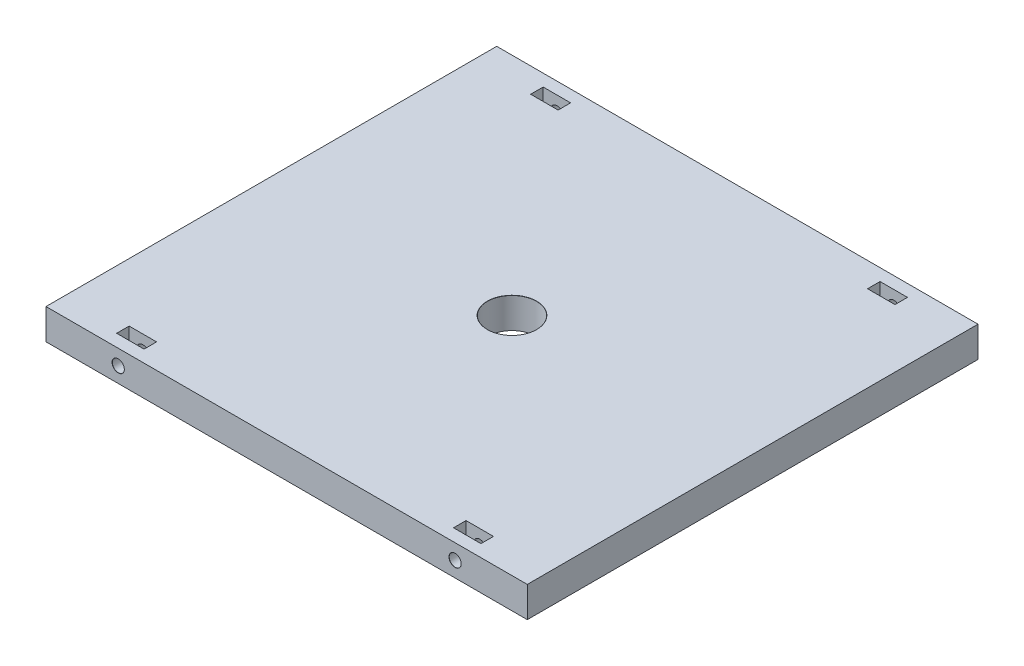
SolidWorks part; units mm, degrees
material "6061 Alloy"
ref_plane "Front Plane" through (0, 0, 0) normal (0, 0, 1) x (1, 0, 0)
ref_plane "Top Plane" through (0, 0, 0) normal (0, 1, 0) x (1, 0, 0)
ref_plane "Right Plane" through (0, 0, 0) normal (1, 0, 0) x (0, 0, -1)
sketch "Sketch1" plane through (0, 0, 0) normal (0, 1, 0) x (1, 0, 0)
  line L1 (-50, -46.825) -> (50, -46.825)
  line L2 (-50, -46.825) -> (-50, 46.825)
  line L3 (-50, 46.825) -> (50, 46.825)
  line L4 (50, -46.825) -> (50, 46.825)
  line L5 (-50, -46.825) -> (50, 46.825) construction
  line L6 (-50, 46.825) -> (50, -46.825) construction
  point P0 (0, 0)
extrude "Boss-Extrude1" add sketch "Sketch1" along normal blind 6.35
sketch "Sketch2" plane through (0, 0, 46.825) normal (0, 0, 1) x (1, 0, 0)
  line L0 (-50, 3.175) -> (-35, 3.175)
  line L1 (-50, 6.35) -> (-50, 0) construction
  line L2 (50, 3.175) -> (35, 3.175)
  line L3 (50, 6.35) -> (50, 0) construction
hole_wizard "Tap Drill for M3x0.5 Tap1" positions "Sketch3" profile "Sketch4" hole size "M3x0.5" standard "ANSI Metric"
sketch "Sketch3" plane through (0, 0, 46.825) normal (0, 0, 1) x (1, 0, 0)
  point P0 (-35, 3.175)
  point P3 (35, 3.175)
sketch "Sketch4" plane through (-35, 3.175, 46.825) normal (1, 0, 0) x (0, -1, 0)
  line L0 (0, 0) -> (0, 10)
  line L1 (0, 10) -> (1.25, 9.2489)
  line L2 (1.25, 9.2489) -> (1.25, 0.025)
  line L3 (1.25, 0.025) -> (1.275, 0)
  line L5 (1.275, 0) -> (0, 0)
  line L6 (-1.25, 0.025) -> (-1.275, 0) construction
  line L10 (0, 10) -> (-1.25, 9.2489) construction
  line L11 (0, -6.35) -> (0, 107.95) construction
  dimension "Hole Dia." = 2.5
  dimension "Hole Depth" = 10
  dimension "Near C'Sink Dia." = 2.55
  dimension "Near C'Sink Angle" = 90
  dimension "Drill Angle" = 118
sketch "Sketch5" plane through (0, 0, -46.825) normal (0, 0, -1) x (-1, 0, 0)
  line L0 (-50, 3.175) -> (-35, 3.175)
  line L1 (50, 3.175) -> (35, 3.175)
hole_wizard "Tap Drill for M3x0.5 Tap2" positions "Sketch6" profile "Sketch7" hole size "M3x0.5" standard "ANSI Metric"
sketch "Sketch6" plane through (0, 0, -46.825) normal (0, 0, -1) x (-1, 0, 0)
  point P0 (-35, 3.175)
  point P3 (35, 3.175)
sketch "Sketch7" plane through (35, 3.175, -46.825) normal (1, 0, 0) x (0, 1, 0)
  line L0 (0, 0) -> (0, 10)
  line L1 (0, 10) -> (1.25, 9.2489)
  line L2 (1.25, 9.2489) -> (1.25, 0.025)
  line L3 (1.25, 0.025) -> (1.275, 0)
  line L5 (1.275, 0) -> (0, 0)
  line L6 (-1.25, 0.025) -> (-1.275, 0) construction
  line L10 (0, 10) -> (-1.25, 9.2489) construction
  line L11 (0, -6.35) -> (0, 107.95) construction
  dimension "Hole Dia." = 2.5
  dimension "Hole Depth" = 10
  dimension "Near C'Sink Dia." = 2.55
  dimension "Near C'Sink Angle" = 90
  dimension "Drill Angle" = 118
hole_wizard "Tap Drill for M12x1.75 Tap1" positions "Sketch9" profile "Sketch10" hole size "M12x1.75" standard "ANSI Metric" end condition through all
sketch "Sketch9" plane through (0, 6.35, 0) normal (0, 1, 0) x (1, 0, 0)
  point P0 (0, 0)
sketch "Sketch10" plane through (0, 6.35, 0) normal (1, 0, 0) x (0, 0, 1)
  line L0 (0, 0) -> (0, 6.35)
  line L1 (0, 6.35) -> (5.1, 6.35)
  line L2 (5.1, 6.35) -> (5.1, 0.025)
  line L3 (5.1, 0.025) -> (5.125, 0)
  line L5 (5.125, 0) -> (0, 0)
  line L6 (-5.1, 0.025) -> (-5.125, 0) construction
  line L11 (0, -6.35) -> (0, 107.95) construction
  dimension "Thru Hole Dia." = 10.2
  dimension "Thru Hole Depth" = 6.35
  dimension "Near C'Sink Dia." = 10.25
  dimension "Near C'Sink Angle" = 90
sketch "Sketch11" plane through (0, 6.35, 0) normal (0, 1, 0) x (1, 0, 0)
  line L0 (33.75, 46.8) -> (36.25, 46.8) construction
  line L1 (-33.725, 46.825) -> (-36.275, 46.825) construction
  line L2 (36.25, -46.8) -> (33.75, -46.8) construction
  line L3 (-33.75, -46.8) -> (-36.25, -46.8) construction
  line L4 (33.75, 46.8) -> (36.25, 46.8) construction
  line L5 (-33.725, 46.825) -> (-36.275, 46.825) construction
  line L6 (36.25, -46.8) -> (33.75, -46.8) construction
  line L7 (-33.75, -46.8) -> (-36.25, -46.8) construction
  line L9 (32.15, -44.3) -> (37.85, -44.3)
  line L10 (32.15, -44.3) -> (32.15, -41.7)
  line L11 (32.15, -41.7) -> (37.85, -41.7)
  line L12 (37.85, -44.3) -> (37.85, -41.7)
  line L13 (32.15, -44.3) -> (37.85, -41.7) construction
  line L14 (32.15, -41.7) -> (37.85, -44.3) construction
  line L15 (-37.85, -44.3) -> (-32.15, -44.3)
  line L16 (-37.85, -44.3) -> (-37.85, -41.7)
  line L17 (-37.85, -41.7) -> (-32.15, -41.7)
  line L18 (-32.15, -44.3) -> (-32.15, -41.7)
  line L19 (-37.85, -44.3) -> (-32.15, -41.7) construction
  line L20 (-37.85, -41.7) -> (-32.15, -44.3) construction
  line L21 (-37.85, 44.325) -> (-32.15, 44.325)
  line L22 (-37.85, 44.325) -> (-37.85, 41.725)
  line L23 (-37.85, 41.725) -> (-32.15, 41.725)
  line L24 (-32.15, 44.325) -> (-32.15, 41.725)
  line L25 (-37.85, 44.325) -> (-32.15, 41.725) construction
  line L26 (-37.85, 41.725) -> (-32.15, 44.325) construction
  line L27 (32.15, 44.325) -> (37.85, 44.325)
  line L28 (32.15, 44.325) -> (32.15, 41.725)
  line L29 (32.15, 41.725) -> (37.85, 41.725)
  line L30 (37.85, 44.325) -> (37.85, 41.725)
  line L31 (32.15, 44.325) -> (37.85, 41.725) construction
  line L32 (32.15, 41.725) -> (37.85, 44.325) construction
  point P8 (35, -43)
  point P13 (-35, -43)
  point P18 (-35, 43.025)
  point P23 (35, 43.025)
  point P29 (-35, 46.825)
  point P30 (-35, -46.8)
  point P31 (35, -46.8)
  point P32 (35, 46.8)
  point P33 (-35, -44.3)
  dimension "D1" = 2.5
  dimension "D2" = 2.5
  dimension "D3" = 5.7
  dimension "D4" = 2.6
extrude "Cut-Extrude1" cut sketch "Sketch11" against normal through all
